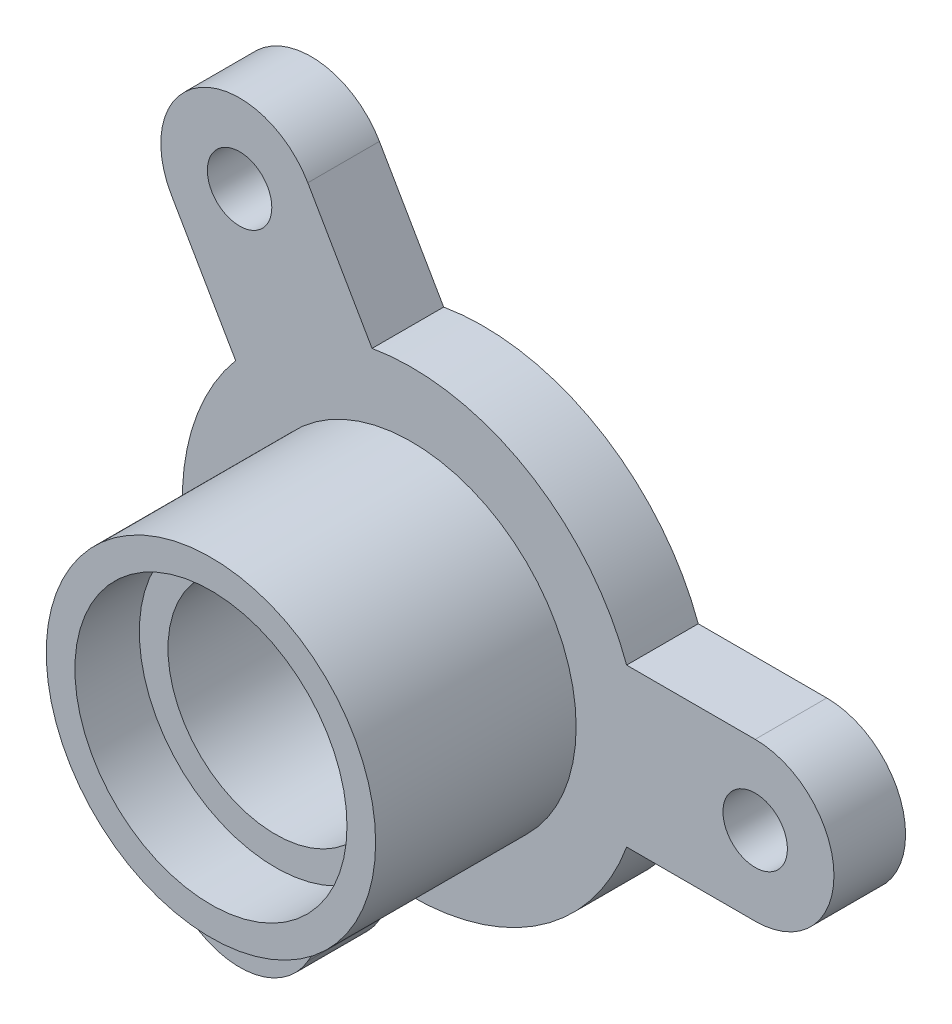
SolidWorks part; units mm, degrees
ref_plane "前视基准面" through (0, 0, 0) normal (0, 0, 1) x (1, 0, 0)
ref_plane "上视基准面" through (0, 0, 0) normal (0, 1, 0) x (1, 0, 0)
ref_plane "右视基准面" through (0, 0, 0) normal (1, 0, 0) x (0, 0, -1)
sketch "草图1" plane through (0, 0, 0) normal (0, 0, 1) x (1, 0, 0)
  circle A0 centre (0, 0) radius 32
extrude "凸台-拉伸1" add sketch "草图1" along normal blind 10
sketch "草图2" plane through (0, 0, 0) normal (0, 0, 1) x (1, 0, 0)
  line L0 (20, -11) -> (48, -11)
  line L1 (48, 11) -> (20, 11)
  arc A0 (48, -11) -> (48, 11) centre (48, 0) ccw
  arc A1 (20, 11) -> (20, -11) centre (20, 0) ccw
extrude "凸台-拉伸2" add sketch "草图2" along normal blind 10
ref_axis "基准轴1" through (0, 0, 10.5) along (0, 0, -1)
pattern_circular "阵列(圆周)1" count 3 over 360 about axis through (0, 0, 10.5) along (0, 0, -1) of "凸台-拉伸2"
ref_plane "基准面1" through (0, 0, 10) normal (0, 0, 1) x (1, 0, 0)
sketch "草图3" plane through (0, 0, 10) normal (0, 0, 1) x (1, 0, 0)
  circle A0 centre (0, 0) radius 23
extrude "凸台-拉伸3" add sketch "草图3" along normal blind 28
ref_plane "基准面2" through (0, 0, 38) normal (0, 0, 1) x (1, 0, 0)
sketch "草图4" plane through (0, 0, 38) normal (0, 0, 1) x (1, 0, 0)
  circle A0 centre (0, 0) radius 15
extrude "切除-拉伸1" cut sketch "草图4" against normal through all
sketch "草图5" plane through (0, 0, 38) normal (0, 0, 1) x (1, 0, 0)
  circle A0 centre (0, 0) radius 19
extrude "切除-拉伸2" cut sketch "草图5" against normal blind 9
sketch "草图6" plane through (0, 0, 10) normal (0, 0, 1) x (1, 0, 0)
  circle A0 centre (48, 0) radius 4.5
  circle A1 centre (-24, 41.5692) radius 4.5
  circle A2 centre (-24, -41.5692) radius 4.5
extrude "切除-拉伸3" cut sketch "草图6" against normal through all
